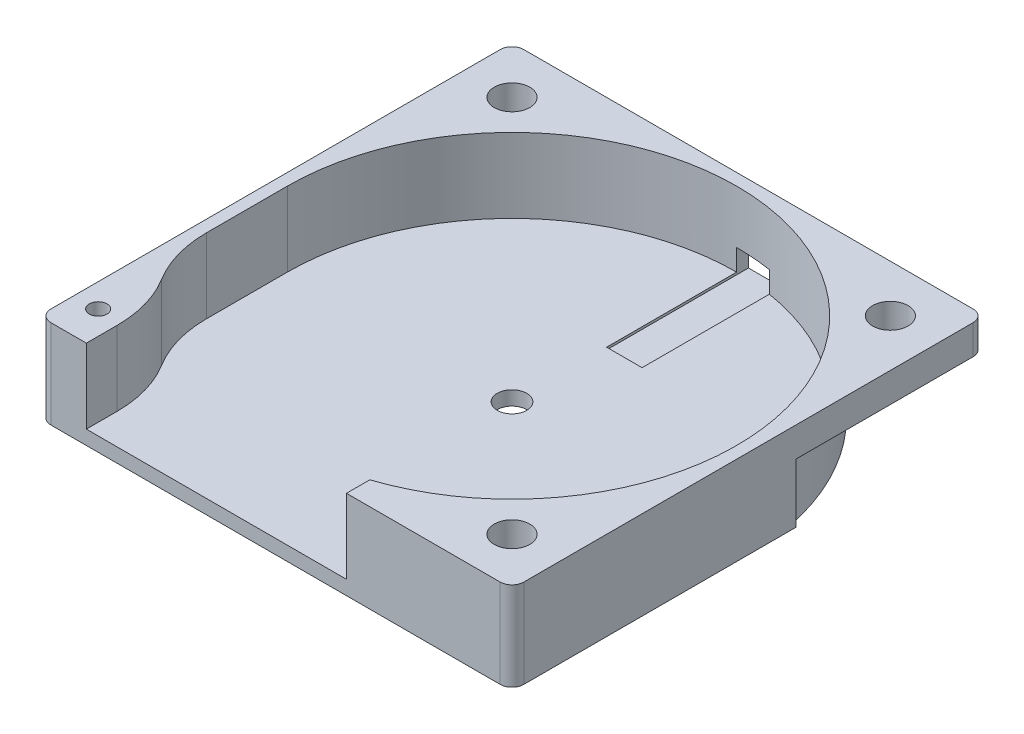
SolidWorks part; units mm, degrees
ref_plane "Front Plane" through (0, 0, 0) normal (0, 0, 1) x (1, 0, 0)
ref_plane "Top Plane" through (0, 0, 0) normal (0, 1, 0) x (1, 0, 0)
ref_plane "Right Plane" through (0, 0, 0) normal (1, 0, 0) x (0, 0, -1)
sketch "Sketch1" plane through (0, 0, 0) normal (0, 1, 0) x (1, 0, 0)
  line L1 (-20, -20) -> (20, -20)
  line L2 (-20, -20) -> (-20, 20)
  line L3 (-20, 20) -> (20, 20)
  line L4 (20, -20) -> (20, 20)
  line L5 (-20, -20) -> (20, 20) construction
  line L6 (-20, 20) -> (20, -20) construction
  point P0 (0, 0)
  dimension "D1" = 40
extrude "Boss-Extrude1" add sketch "Sketch1" along normal blind 7.5
sketch "Sketch2" plane through (0, 7.5, 0) normal (0, 1, 0) x (1, 0, 0)
  circle A0 centre (0, 0) radius 19
  dimension "D1" = 38
extrude "Cut-Extrude1" cut sketch "Sketch2" against normal offset from surface (6.3 mm away) 1.2 up to face at (0, 0, 0)
sketch "Sketch3" plane through (0, 7.5, 0) normal (0, 1, 0) x (1, 0, 0)
  line L0 (-20, -20) -> (20, -20) construction
  line L1 (-19, 0) -> (6, 0)
  line L2 (-19, 0) -> (-19, -20)
  line L3 (-19, -20) -> (6, -20)
  line L4 (6, 0) -> (6, -20)
  circle A0 centre (0, 0) radius 19 construction
  dimension "D1" = 25
extrude "Cut-Extrude2" cut sketch "Sketch3" against normal up to surface (6.3 mm away) up to face at (0, 1.2, -19)
sketch "Sketch4" plane through (0, 7.5, 0) normal (0, 1, 0) x (1, 0, 0)
  line L1 (-16, -16) -> (16, -16) construction
  line L2 (-16, -16) -> (-16, 16) construction
  line L3 (-16, 16) -> (16, 16) construction
  line L4 (16, -16) -> (16, 16) construction
  line L5 (-16, -16) -> (16, 16) construction
  line L6 (-16, 16) -> (16, -16) construction
  circle A0 centre (-16, 16) radius 1.5
  circle A1 centre (16, 16) radius 1.5
  circle A2 centre (16, -16) radius 1.5
  point P6 (0, 0)
  dimension "D2" = 3
  dimension "D1" = 32
extrude "Cut-Extrude3" cut sketch "Sketch4" against normal through all
sketch "Sketch5" plane through (0, 7.5, 0) normal (0, 1, 0) x (1, 0, 0)
  circle A0 centre (-16, 16) radius 3
  circle A1 centre (16, 16) radius 3
  circle A2 centre (16, -16) radius 3
  dimension "D1" = 6
extrude "Cut-Extrude4" [suppressed] cut sketch "Sketch5" against normal blind 9
sketch "Sketch6" plane through (0, 1.2, 0) normal (0, 1, 0) x (1, 0, 0)
  circle A0 centre (0, 0) radius 1.25
  dimension "D1" = 2.5
extrude "Cut-Extrude5" cut sketch "Sketch6" against normal through all
sketch "Sketch7" plane through (0, 1.2, 0) normal (0, 1, 0) x (1, 0, 0)
  line L1 (-19, -20) -> (-16, -20)
  line L2 (-19, -20) -> (-19, -14)
  line L3 (-19, -14) -> (-16, -14)
  line L4 (-16, -20) -> (-16, -14)
  dimension "D1" = 6
  dimension "D2" = 3
extrude "Boss-Extrude2" add sketch "Sketch7" along normal up to surface (6.3 mm away) up to face at (-16, 7.5, -14.5)
fillet "Fillet1" radius 10 1 edges at (-19, 4.35, 14)
fillet "Fillet2" radius 10 1 edges at (-16, 4.35, 14)
sketch "Sketch8" plane through (0, 7.5, 0) normal (0, 1, 0) x (1, 0, 0)
  line L0 (-20, 20) -> (-20, -20) construction
  line L1 (-20, -20) -> (-16, -20) construction
  circle A0 centre (-18, -17) radius 0.75
  dimension "D1" = 1.5
  dimension "D2" = 2
  dimension "D3" = 3
extrude "Cut-Extrude6" cut sketch "Sketch8" against normal through all
sketch "Sketch9" plane through (0, 0, 20) normal (0, 0, 1) x (1, 0, 0)
  line L0 (-18, 7.5) -> (-16, 7.5)
  line L1 (-16, 7.5) -> (-16, 1.2)
  line L2 (-16, 1.2) -> (6, 1.2)
  line L3 (6, 1.2) -> (6, 7.5)
  line L4 (6, 7.5) -> (8, 7.5)
  line L5 (6, 7.5) -> (20, 7.5) construction
  line L6 (8, 7.5) -> (8, 0)
  line L7 (-20, 0) -> (20, 0) construction
  line L8 (8, 0) -> (-18, 0)
  line L9 (-18, 0) -> (-18, 7.5)
  line L10 (-20, 7.5) -> (-16, 7.5) construction
  dimension "D1" = 2
extrude "Boss-Extrude3" add sketch "Sketch9" along normal blind 5
fillet "Fillet3" radius 1 4 edges at (-20, 3.75, 20) (-20, 3.75, -20) (20, 3.75, -20) (20, 3.75, 20)
sketch "Sketch10" plane through (0, 0, 0) normal (0, -1, 0) x (1, 0, 0)
  line L0 (19, -20) -> (-19, -20) construction
  line L1 (0, -8) -> (3, -8)
  line L2 (0, -8) -> (0, -20)
  line L3 (0, -20) -> (3, -20)
  line L4 (3, -8) -> (3, -20)
  dimension "D1" = 3
  dimension "D2" = 8
extrude "Cut-Extrude7" cut sketch "Sketch10" against normal blind 2 from offset 1 offset against normal yes
sketch "Sketch11" plane through (0, 0, 0) normal (1, 0, 0) x (0, 0, -1)
  line L4 (-20, 0) -> (-20, 7.5)
  line L5 (-20, 7.5) -> (-25, 7.5)
  line L6 (-25, 7.5) -> (-25, 0)
  line L7 (-25, 0) -> (-20, 0)
  line L8 (-20, 0) -> (-20, 7.5)
  line L9 (-20, 7.5) -> (-25, 7.5)
  line L10 (-25, 7.5) -> (-25, 0)
  line L11 (-25, 0) -> (-20, 0)
  dimension "D1" = 0
extrude "Cut-Extrude8" cut sketch "Sketch11" against normal through all both and the other way through all
sketch "Sketch12" plane through (0, 0, 0) normal (0, -1, 0) x (1, 0, 0)
  line L0 (18.5742, -4) -> (20, -4)
  line L1 (-18.5742, -4) -> (-20, -4)
  line L2 (4, -20) -> (4, -18.5742)
  line L3 (-4, -20) -> (-4, -18.5742)
  line L8 (-16, 20) -> (-19, 20)
  line L9 (-16, 17.3942) -> (-16, 20)
  line L10 (-19, 0) -> (-19, 6.8586)
  line L11 (6, 20) -> (6, 18.0278)
  line L12 (19, 20) -> (6, 20)
  line L13 (20, -19) -> (20, 19)
  line L14 (-19, -20) -> (19, -20)
  line L15 (-20, 19) -> (-20, -19)
  line L16 (-16, 20) -> (-19, 20)
  line L17 (-16, 17.3942) -> (-16, 20)
  line L18 (-19, 0) -> (-19, 6.8586)
  line L19 (6, 20) -> (6, 18.0278)
  line L20 (19, 20) -> (6, 20)
  line L21 (20, -19) -> (20, 19)
  line L22 (-19, -20) -> (19, -20)
  line L23 (-20, 19) -> (-20, -19)
  circle A0 centre (16, -16) radius 1.5 construction
  circle A1 centre (-16, -16) radius 1.5 construction
  circle A2 centre (16, -16) radius 1.5
  circle A3 centre (-16, -16) radius 1.5
  circle A4 centre (0, 0) radius 20
  arc A7 (-17.5, 12.1264) -> (-16, 17.3942) centre (-26, 17.3942) ccw
  arc A8 (-17.5, 12.1264) -> (-19, 6.8586) centre (-9, 6.8586) ccw
  arc A9 (-19, 0) -> (6, 18.0278) centre (0, 0) ccw
  arc A10 (20, 19) -> (19, 20) centre (19, 19) ccw
  arc A11 (19, -20) -> (20, -19) centre (19, -19) ccw
  arc A12 (-20, -19) -> (-19, -20) centre (-19, -19) ccw
  arc A13 (-19, 20) -> (-20, 19) centre (-19, 19) ccw
  arc A14 (-17.5, 12.1264) -> (-16, 17.3942) centre (-26, 17.3942) ccw
  arc A15 (-17.5, 12.1264) -> (-19, 6.8586) centre (-9, 6.8586) ccw
  arc A16 (-19, 0) -> (6, 18.0278) centre (0, 0) ccw
  arc A17 (20, 19) -> (19, 20) centre (19, 19) ccw
  arc A18 (19, -20) -> (20, -19) centre (19, -19) ccw
  arc A19 (-20, -19) -> (-19, -20) centre (-19, -19) ccw
  arc A20 (-19, 20) -> (-20, 19) centre (-19, 19) ccw
  line M24 (-20, 19) -> (-20, -19)
  arc M25 (-20, -19) -> (-19, -20) centre (-19, -19) ccw
  line M26 (-19, -20) -> (19, -20)
  arc M27 (19, -20) -> (20, -19) centre (19, -19) ccw
  line M28 (20, -19) -> (20, 19)
  circle M32 centre (-16, -16) radius 1.5
  circle M33 centre (16, -16) radius 1.5
  dimension "D5" = 40
  dimension "D2" = 16
  dimension "D3" = 16
  dimension "D4" = 16
  dimension "D1" = 0
extrude "Cut-Extrude9" cut sketch "Sketch12" against normal blind 5 contours A16 L2 L0 M26 M27 M28 M33 | A16 L1 L3 M24 M25 M26 M32 region at (19.798, 0, -4.2263) region at (-4.2263, 0, -19.798)
